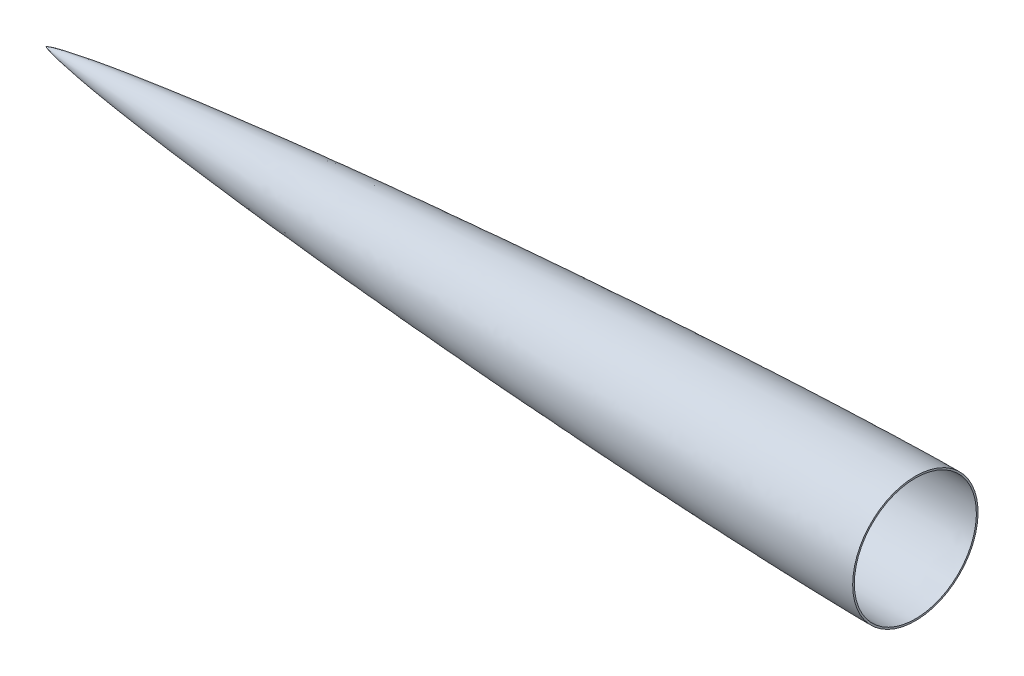
SolidWorks part; units mm, degrees
material "Thornel VCB-20 Carbon Cloth"
ref_plane "Front Plane" through (0, 0, 0) normal (0, 0, 1) x (1, 0, 0)
ref_plane "Top Plane" through (0, 0, 0) normal (0, 1, 0) x (1, 0, 0)
ref_plane "Right Plane" through (0, 0, 0) normal (1, 0, 0) x (0, 0, -1)
sketch "Sketch2" plane through (0, 0, 0) normal (0, 0, 1) x (1, 0, 0)
  line L0 (0, 0) -> (1040, 0) construction
  line L1 (1040, 75) -> (1040, 0) construction
  line L2 (0, 0) -> (6.0831, 0)
  line L3 (1040, 75) -> (1040.0036, 73)
  line L4 (6.0831, 0) -> (19.7005, -4.7407) construction
  line L5 (0, 0) -> (19.0429, -6.6295) construction
  spline S0 degree 4 poles (0, 0) (0.0022, 0.0047) (0.0073, 0.0137) (0.0201, 0.0298) (0.0505, 0.058) (0.0952, 0.0928) (0.1553, 0.133) (0.2436, 0.1861) (0.3523, 0.2452) (0.5135, 0.3254) (0.7288, 0.4227) (0.9812, 0.5277) (1.2707, 0.6398) (1.588, 0.7559) (1.9332, 0.8758) (2.4999, 1.0636) (3.5152, 1.3768) (5.368, 1.896) (8.8624, 2.7652) (15.3472, 4.178) (27.6305, 6.4922) (49.7383, 10.0558) (85.9006, 15.0416) (134.608, 20.8316) (192.8236, 26.9438) (256.11, 32.918) (319.4421, 38.3828) (382.8092, 43.4231) (446.2048, 48.0921) (509.6243, 52.4219) (573.0648, 56.4324) (636.5242, 60.1328) (700.0008, 63.5239) (763.4936, 66.5974) (827.0019, 69.3342) (882.5848, 71.4034) (930.2366, 72.9052) (968.7778, 73.9051) (994.8196, 74.455) (1016.3039, 74.8021) (1029.8443, 74.9475) (1036.6147, 74.9939) (1040, 75) knots 0 0 0 0 0 0.00002 0.00004 0.000079 0.000158 0.000237 0.000316 0.000474 0.000632 0.000927 0.001222 0.001522 0.001821 0.002222 0.002622 0.00381 0.005893 0.009596 0.016421 0.029243 0.053793 0.095411 0.156318 0.217224 0.278131 0.339037 0.399944 0.46085 0.521757 0.582663 0.64357 0.704476 0.765383 0.826289 0.887196 0.917649 0.948102 0.974051 0.987026 1 1 1 1 1 construction
  spline S1 degree 4 poles (0, 0) (0.0022, 0.0047) (0.0073, 0.0137) (0.0201, 0.0298) (0.0505, 0.058) (0.0952, 0.0928) (0.1553, 0.133) (0.2436, 0.1861) (0.3523, 0.2452) (0.5135, 0.3254) (0.7288, 0.4227) (0.9812, 0.5277) (1.2707, 0.6398) (1.588, 0.7559) (1.9332, 0.8758) (2.4999, 1.0636) (3.5152, 1.3768) (5.368, 1.896) (8.8624, 2.7652) (15.3472, 4.178) (27.6305, 6.4922) (49.7383, 10.0558) (85.9006, 15.0416) (134.608, 20.8316) (192.8236, 26.9438) (256.11, 32.918) (319.4421, 38.3828) (382.8092, 43.4231) (446.2048, 48.0921) (509.6243, 52.4219) (573.0648, 56.4324) (636.5242, 60.1328) (700.0008, 63.5239) (763.4936, 66.5974) (827.0019, 69.3342) (882.5848, 71.4034) (930.2366, 72.9052) (968.7778, 73.9051) (994.8196, 74.455) (1016.3039, 74.8021) (1029.8443, 74.9475) (1036.6147, 74.9939) (1040, 75) knots 0 0 0 0 0 0.00002 0.00004 0.000079 0.000158 0.000237 0.000316 0.000474 0.000632 0.000927 0.001222 0.001522 0.001821 0.002222 0.002622 0.00381 0.005893 0.009596 0.016421 0.029243 0.053793 0.095411 0.156318 0.217224 0.278131 0.339037 0.399944 0.46085 0.521757 0.582663 0.64357 0.704476 0.765383 0.826289 0.887196 0.917649 0.948102 0.974051 0.987026 1 1 1 1 1
  spline S2 degree 1 poles (6.0831, 0) (1040.0036, 73) knots 0 0 1 1 construction
  spline S3 degree 3 poles (6.0831, 0) (8.6666, 0.6715) (13.8671, 1.8201) (24.4405, 3.8664) (37.7262, 6.0978) (53.7347, 8.5166) (75.1212, 11.5008) (101.9111, 14.8997) (134.106, 18.6384) (166.3345, 22.1189) (209.3372, 26.4875) (263.137, 31.5223) (327.7463, 37.0451) (392.3932, 42.1335) (457.0702, 46.8409) (543.3399, 52.6515) (651.2312, 59.0924) (759.1804, 64.4662) (845.5698, 68.0513) (910.3751, 70.3358) (964.391, 71.8345) (1002.2021, 72.5879) (1023.8112, 72.8888) (1034.6051, 72.9903) (1040.0036, 73) knots 0.005686 0.005686 0.005686 0.005686 0.013454 0.021222 0.036758 0.052295 0.067831 0.098903 0.129975 0.161048 0.19212 0.254265 0.316409 0.378554 0.440698 0.502843 0.627132 0.751422 0.813566 0.875711 0.937855 0.968928 0.984464 1 1 1 1
  dimension "D1" = 75
  dimension "D2" = 1040
  dimension "D3" = 2
revolve "Revolve1" add sketch "Sketch2" angle 360 about L0
